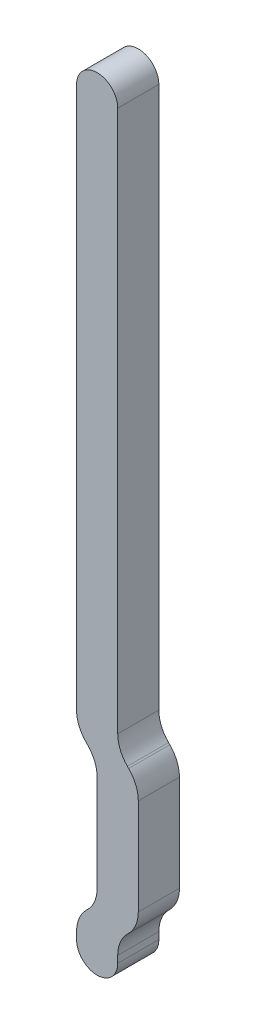
SolidWorks part; units mm, degrees
ref_plane "前视基准面" through (0, 0, 0) normal (0, 0, 1) x (1, 0, 0)
ref_plane "上视基准面" through (0, 0, 0) normal (0, 1, 0) x (1, 0, 0)
ref_plane "右视基准面" through (0, 0, 0) normal (1, 0, 0) x (0, 0, -1)
sketch "草图1" plane through (0, 0, 0) normal (0, 0, 1) x (1, 0, 0)
  line L0 (-5, -175) -> (-5, -180)
  line L1 (-5, -175) -> (0, -170)
  line L2 (0, -170) -> (0, -140)
  line L3 (0, -140) -> (-5, -135)
  line L4 (-5, -135) -> (-5, 0)
  line L8 (5, -135) -> (10, -140)
  line L9 (10, -140) -> (10, -170)
  line L10 (10, -170) -> (5, -175)
  line L12 (5, -180) -> (5, -175)
  line L13 (5, -135) -> (5, 0)
  arc A10 (-5, 0) -> (5, 0) centre (0, 0) cw
  arc A11 (5, -180) -> (-5, -180) centre (0, -180) cw
extrude "凸台-拉伸1" add sketch "草图1" along normal blind 10
fillet "圆角1" radius 8 8 edges at (-5, -135, 5) (0, -140, 5) (0, -170, 5) (-5, -175, 5) (5, -175, 5) (10, -170, 5) (10, -140, 5) (5, -135, 5)
